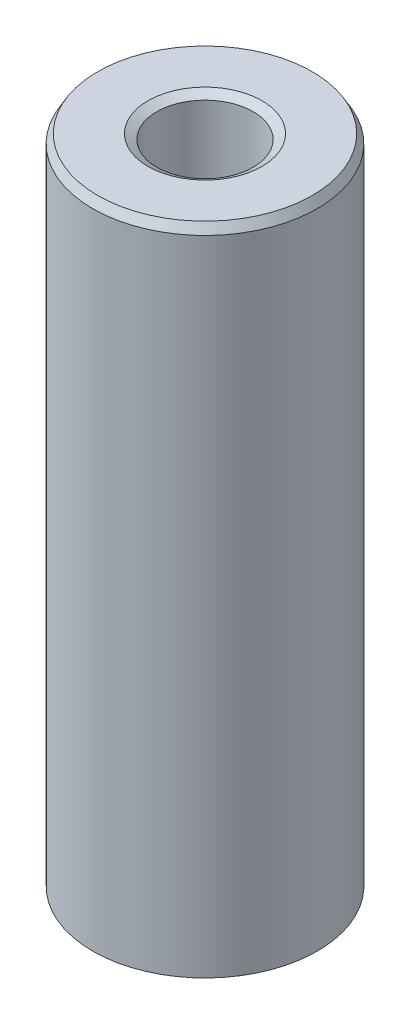
SolidWorks part; units mm, degrees
ref_plane "Front Plane" through (0, 0, 0) normal (0, 0, 1) x (1, 0, 0)
ref_plane "Top Plane" through (0, 0, 0) normal (0, 1, 0) x (1, 0, 0)
ref_plane "Right Plane" through (0, 0, 0) normal (1, 0, 0) x (0, 0, -1)
sketch "Sketch1" plane through (0, 0, 0) normal (0, 1, 0) x (1, 0, 0)
  circle A0 centre (0, 0) radius 32.5
  dimension "SLEEVE_OD" = 65
extrude "Boss-Extrude1" add sketch "Sketch1" along normal blind 190.0201
sketch "Sketch2" plane through (0, 0, 0) normal (0, 1, 0) x (1, 0, 0)
  circle A0 centre (0, 0) radius 13.9374
  dimension "BORE_D" = 27.8747
extrude "Cut-Extrude1" cut sketch "Sketch2" along normal through all
chamfer "Chamfer1" distance 2.5456 angle 30 4 edges at (0, 190.0201, 13.9374) (0, 0, 13.9374) (0, 0, 32.5) (0, 190.0201, 32.5) first distance on face at (0, 190.0201, 13.9374) first distance on face at (0, 0, 13.9374) first distance on face at (0, 190.0201, 32.5)
